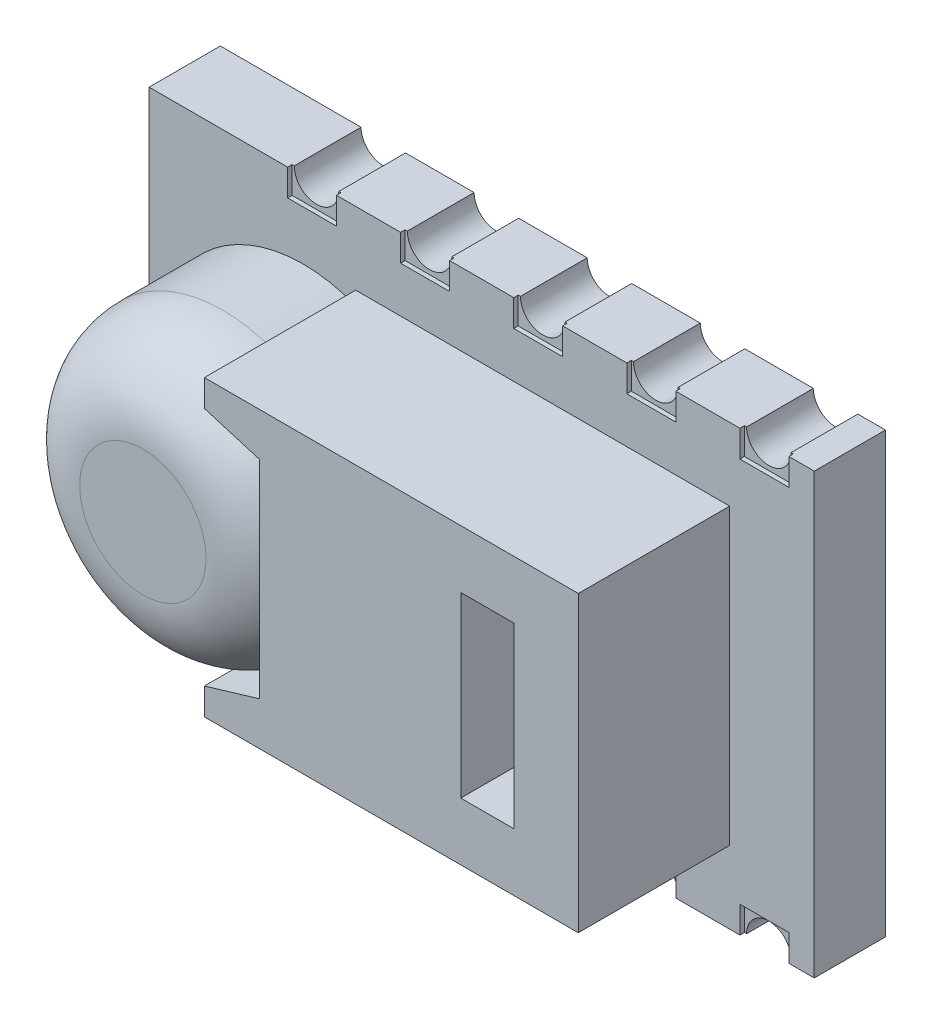
SolidWorks part; units mm, degrees
ref_plane "Front Plane" through (0, 0, 0) normal (0, 0, 1) x (1, 0, 0)
ref_plane "Top Plane" through (0, 0, 0) normal (0, 1, 0) x (1, 0, 0)
ref_plane "Right Plane" through (0, 0, 0) normal (1, 0, 0) x (0, 0, -1)
sketch "Sketch1" plane through (0, 0, 0) normal (0, 0, 1) x (1, 0, 0)
  line L1 (0, 0) -> (7.47, 0)
  line L2 (0, 0) -> (0, 4.93)
  line L3 (0, 4.93) -> (7.47, 4.93)
  line L4 (7.47, 0) -> (7.47, 4.93)
  dimension "D1" = 4.93
  dimension "D2" = 7.47
extrude "Boss-Extrude1" add sketch "Sketch1" along normal blind 0.8
sketch "Sketch2" plane through (0, 0, 0.8) normal (0, 0, 1) x (1, 0, 0)
  line L0 (0, 2.465) -> (7.47, 2.465) construction
  line L1 (0, 4.93) -> (0, 0) construction
  line L2 (7.47, 0) -> (7.47, 4.93) construction
  line L3 (2.9396, 3.6294) -> (2.9396, 1.3006)
  line L4 (6.52, 4.115) -> (2.32, 4.115)
  line L5 (6.52, 4.115) -> (6.52, 0.815)
  line L6 (6.52, 0.815) -> (2.32, 0.815)
  line L7 (2.32, 4.115) -> (2.32, 3.815)
  line L8 (2.32, 3.815) -> (2.9396, 3.6294)
  line L9 (2.32, 1.115) -> (2.9396, 1.3006)
  line L10 (2.32, 1.115) -> (2.32, 0.815)
  point P10 (6.52, 2.465)
  point P13 (2.9396, 2.465)
  dimension "D1" = 3.3
  dimension "D2" = 4.2
  dimension "D3" = 0.95
  dimension "D4" = 0.3
  dimension "D5" = 0.3
extrude "Boss-Extrude2" add sketch "Sketch2" along normal blind 1.7
sketch "Sketch3" plane through (0, 0, 0.8) normal (0, 0, 1) x (1, 0, 0)
  line L0 (0, 2.465) -> (2.9396, 2.465) construction
  line L1 (0, 4.93) -> (0, 0) construction
  line L2 (2.9396, 3.6294) -> (2.9396, 1.3006) construction
  line L3 (0.12, 2.465) -> (0.12, 4.0746) construction
  line L4 (2.32, 4.115) -> (2.32, 3.815) construction
  circle A0 centre (1.7296, 2.465) radius 1.6096
  dimension "D2" = 3.2193
  dimension "D1" = 2.2
extrude "Boss-Extrude3" add sketch "Sketch3" along normal blind 1.8
fillet "Fillet1" radius 0.9 1 edges at (3.3393, 2.465, 2.6)
sketch "Sketch4" plane through (0, 0, 2.5) normal (0, 0, 1) x (1, 0, 0)
  line L0 (6.52, 2.465) -> (2.9396, 2.465) construction
  line L1 (6.52, 0.815) -> (6.52, 4.115) construction
  line L2 (2.9396, 3.6294) -> (2.9396, 1.3006) construction
  line L3 (0, 4.93) -> (0, 0) construction
  line L4 (5.8, 3.465) -> (5.2, 3.465)
  line L5 (5.8, 3.465) -> (5.8, 1.465)
  line L6 (5.8, 1.465) -> (5.2, 1.465)
  line L7 (5.2, 3.465) -> (5.2, 1.465)
  point P12 (5.8, 2.465)
  dimension "D1" = 2
  dimension "D2" = 0.6
  dimension "D3" = 5.2
extrude "Cut-Extrude1" cut sketch "Sketch4" against normal blind 1.8
sketch "Sketch5" plane through (0, 0, 0.8) normal (0, 0, 1) x (1, 0, 0)
  line L0 (7.47, 4.93) -> (0, 4.93) construction
  line L1 (1.58, 4.93) -> (2.08, 4.93)
  line L2 (0, 4.93) -> (0, 0) construction
  arc A0 (2.08, 4.93) -> (1.58, 4.93) centre (1.83, 4.93) cw
  dimension "D2" = 0.25
  dimension "D1" = 1.83
extrude "Cut-Extrude2" cut sketch "Sketch5" against normal through all
sketch "Sketch6" plane through (0, 0, 0.8) normal (0, 0, 1) x (1, 0, 0)
  line L0 (1.58, 4.93) -> (0, 4.93) construction
  line L1 (1.555, 4.93) -> (2.105, 4.93)
  line L2 (1.555, 4.93) -> (1.555, 4.63)
  line L3 (1.555, 4.63) -> (2.105, 4.63)
  line L4 (2.105, 4.93) -> (2.105, 4.63)
  line L5 (1.83, 4.93) -> (1.83, 4.3392) construction
  point P9 (1.83, 4.63)
  dimension "D1" = 0.3
  dimension "D2" = 0.55
extrude "Cut-Extrude3" cut sketch "Sketch6" against normal blind 0.05
pattern_linear "LPattern1" count 5 spacing 1.27 along (1, 0, 0) of "Cut-Extrude2", "Cut-Extrude3"
ref_plane "Plane1" through (0, 2.465, 0) normal (0, 1, 0) x (1, 0, 0)
mirror "Mirror1" about plane through (0, 2.465, 0) normal (0, 1, 0) of "LPattern1"
